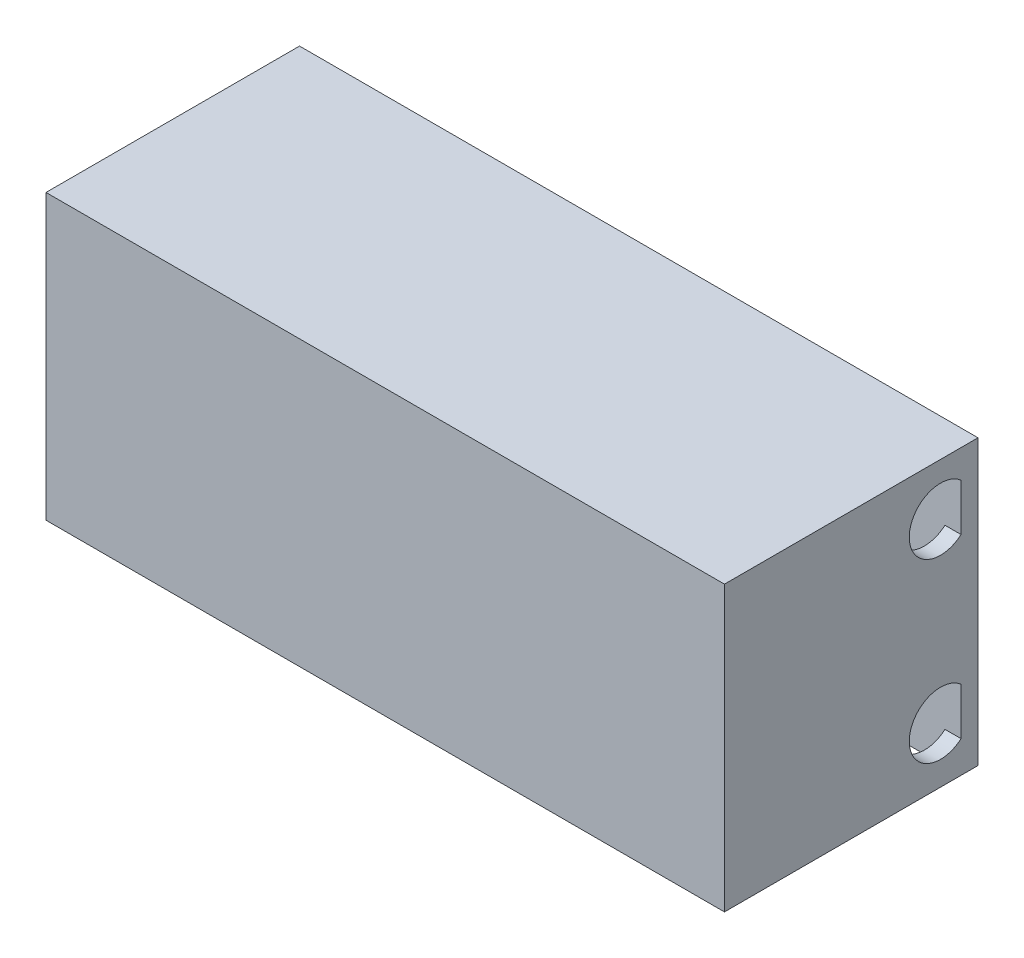
SolidWorks part; units mm, degrees
ref_plane "Front" through (0, 0, 0) normal (0, 0, 1) x (1, 0, 0)
ref_plane "Top" through (0, 0, 0) normal (0, 1, 0) x (1, 0, 0)
ref_plane "Right" through (0, 0, 0) normal (1, 0, 0) x (0, 0, -1)
sketch "Sketch1" plane through (0, 0, 0) normal (0, 1, 0) x (1, 0, 0)
  line L1 (0, 0) -> (-76, 0)
  line L2 (0, 0) -> (0, 28.4)
  line L3 (0, 28.4) -> (-76, 28.4)
  line L4 (-76, 0) -> (-76, 28.4)
  dimension "D1" = 28.4
  dimension "D2" = 76
extrude "Boss-Extrude1" add sketch "Sketch1" along normal blind 1.8
sketch "Sketch2" plane through (0, 0, 0) normal (0, -1, 0) x (-1, 0, 0)
  line L0 (0, 0) -> (0, 28.4) construction
  line L1 (76, 28.4) -> (0, 28.4)
  line L2 (76, 28.4) -> (76, 26.6)
  line L3 (76, 26.6) -> (0, 26.6)
  line L4 (0, 28.4) -> (0, 26.6)
  dimension "D1" = 1.8
extrude "Boss-Extrude2" add sketch "Sketch2" along normal blind 30
sketch "Sketch3" plane through (0, 0, 0) normal (0, -1, 0) x (-1, 0, 0)
  line L0 (0, 26.6) -> (76, 26.6) construction
  line L1 (76, 0) -> (74.2, 0)
  line L2 (76, 0) -> (76, 26.6)
  line L3 (76, 26.6) -> (74.2, 26.6)
  line L4 (74.2, 0) -> (74.2, 26.6)
  line L6 (0, 0) -> (1.8, 0)
  line L7 (0, 0) -> (0, 26.6)
  line L8 (0, 26.6) -> (1.8, 26.6)
  line L9 (1.8, 0) -> (1.8, 26.6)
  dimension "D1" = 1.8
  dimension "D2" = 1.8
extrude "Boss-Extrude3" add sketch "Sketch3" along normal blind 30
sketch "Sketch4" plane through (0, 0, 0) normal (0, -1, 0) x (-1, 0, 0)
  line L0 (1.8, 0) -> (1.8, 26.6) construction
  line L1 (1.8, 18.5) -> (74.2, 18.5)
  line L2 (1.8, 18.5) -> (1.8, 19.7)
  line L3 (1.8, 19.7) -> (74.2, 19.7)
  line L4 (74.2, 18.5) -> (74.2, 19.7)
  line L5 (74.2, 26.6) -> (74.2, 0) construction
  line L6 (1.8, 26.6) -> (74.2, 26.6) construction
  line L7 (1.8, 21.5) -> (74.2, 21.5)
  line L8 (1.8, 21.5) -> (1.8, 22.7)
  line L9 (1.8, 22.7) -> (74.2, 22.7)
  line L10 (74.2, 21.5) -> (74.2, 22.7)
  dimension "D1" = 1.2
  dimension "D2" = 1.2
  dimension "D3" = 1.8
  dimension "D4" = 3.9
extrude "Boss-Extrude4" add sketch "Sketch4" along normal blind 1
sketch "Sketch5" plane through (0, -1, 0) normal (0, -1, 0) x (-1, 0, 0)
  line L0 (74.2, 19.7) -> (1.8, 19.7) construction
  line L1 (1.8, 18.5) -> (6.8, 18.5)
  line L2 (1.8, 18.5) -> (1.8, 19.7)
  line L3 (1.8, 19.7) -> (6.8, 19.7)
  line L4 (6.8, 18.5) -> (6.8, 19.7)
  line L6 (74.2, 18.5) -> (69.2, 18.5)
  line L7 (74.2, 18.5) -> (74.2, 19.7)
  line L8 (74.2, 19.7) -> (69.2, 19.7)
  line L9 (69.2, 18.5) -> (69.2, 19.7)
  dimension "D1" = 5
  dimension "D2" = 5
extrude "Boss-Extrude5" add sketch "Sketch5" along normal blind 28
sketch "Sketch6" plane through (-74.2, 0, 0) normal (1, 0, 0) x (0, 0, -1)
  line L1 (21.5, -1) -> (24.3, -1)
  line L2 (21.5, -1) -> (21.5, -11)
  line L3 (21.5, -11) -> (24.3, -11)
  line L4 (24.3, -1) -> (24.3, -11)
  point P5 (0, 0)
  dimension "D1" = 2.8
  dimension "D2" = 10
extrude "Cut-Extrude1" cut sketch "Sketch6" against normal blind 2
sketch "Sketch7" plane through (0, 0, 0) normal (0, -1, 0) x (-1, 0, 0)
  line L0 (1.8, 21.5) -> (74.2, 21.5) construction
  line L1 (69.2, 24.3) -> (74.2, 24.3)
  line L2 (69.2, 24.3) -> (69.2, 25.5)
  line L3 (69.2, 25.5) -> (74.2, 25.5)
  line L4 (74.2, 24.3) -> (74.2, 25.5)
  line L5 (74.2, 26.6) -> (74.2, 22.7) construction
  dimension "D1" = 2.8
  dimension "D2" = 1.2
  dimension "D3" = 5
  dimension "D4" = 0
extrude "Boss-Extrude6" add sketch "Sketch7" along normal blind 10
sketch "Sketch8" plane through (0, -1, 0) normal (0, -1, 0) x (-1, 0, 0)
  line L0 (74.2, 22.7) -> (1.8, 22.7) construction
  line L1 (1.8, 21.5) -> (9.8, 21.5)
  line L2 (1.8, 21.5) -> (1.8, 22.7)
  line L3 (1.8, 22.7) -> (9.8, 22.7)
  line L4 (9.8, 21.5) -> (9.8, 22.7)
  dimension "D1" = 8
extrude "Cut-Extrude2" cut sketch "Sketch8" against normal blind 0.7
sketch "Sketch9" plane through (0, 0, 0) normal (0, -1, 0) x (-1, 0, 0)
  line L0 (1.8, 22.7) -> (1.8, 26.6) construction
  line L1 (11.8, 26.6) -> (1.8, 26.6)
  line L2 (11.8, 26.6) -> (11.8, 26.5)
  line L3 (11.8, 26.5) -> (1.8, 26.5)
  line L4 (1.8, 26.6) -> (1.8, 26.5)
  line L5 (74.2, 19.7) -> (1.8, 19.7) construction
  dimension "D1" = 0.1
  dimension "D2" = 6.8
  dimension "D3" = 10
extrude "Boss-Extrude7" add sketch "Sketch9" along normal blind 30
sketch "Sketch10" plane through (-1.8, 0, 0) normal (-1, 0, 0) x (0, 0, 1)
  line L0 (-19.7, -29) -> (-19.7, 0) construction
  line L1 (-22.7, 0) -> (-26.5, 0) construction
  line L2 (-26.5, -6.6382) -> (-26.5, -1.3618)
  line L3 (-26.5, -30) -> (-26.5, 0) construction
  line L4 (-26.5, -21.1618) -> (-26.5, -26.4382)
  line L6 (-26.5, -30) -> (-26.5, 0) construction
  arc A0 (-26.5, -6.6382) -> (-26.5, -1.3618) centre (-24.2, -4) ccw
  arc A1 (-26.5, -26.4382) -> (-26.5, -21.1618) centre (-24.2, -23.8) ccw
  dimension "D1" = 7
  dimension "D2" = 7
  dimension "D3" = 4.5
  dimension "D4" = 4.5
  dimension "D5" = 4
  dimension "D6" = 19.8
extrude "Cut-Extrude3" cut sketch "Sketch10" against normal blind 2
sketch "Sketch11" plane through (0, -1, 0) normal (0, -1, 0) x (-1, 0, 0)
  line L1 (6.8, 18.5) -> (69.2, 18.5)
  line L2 (6.8, 18.5) -> (6.8, 19.7)
  line L3 (6.8, 19.7) -> (69.2, 19.7)
  line L4 (69.2, 18.5) -> (69.2, 19.7)
extrude "Boss-Extrude8" add sketch "Sketch11" along normal blind 28
sketch "Sketch12" plane through (0, 0, 0) normal (0, -1, 0) x (1, 0, 0)
  line L0 (-1.8, 0) -> (-1.8, -18.5) construction
  line L1 (-1.8, -8.3) -> (-74.2, -8.3)
  line L2 (-1.8, -8.3) -> (-1.8, -7.1)
  line L3 (-1.8, -7.1) -> (-74.2, -7.1)
  line L4 (-74.2, -8.3) -> (-74.2, -7.1)
  line L5 (-74.2, -18.5) -> (-74.2, 0) construction
  line L6 (-1.8, -18.5) -> (-74.2, -18.5) construction
  dimension "D1" = 10.2
  dimension "D2" = 1.2
extrude "Boss-Extrude9" add sketch "Sketch12" along normal blind 29
sketch "Sketch13" plane through (0, 0, 0) normal (0, -1, 0) x (-1, 0, 0)
  line L0 (1.8, 0) -> (1.8, 7.1) construction
  line L1 (1.8, 5.1) -> (74.2, 5.1)
  line L2 (1.8, 5.1) -> (1.8, 3.9)
  line L3 (1.8, 3.9) -> (74.2, 3.9)
  line L4 (74.2, 5.1) -> (74.2, 3.9)
  line L5 (74.2, 7.1) -> (74.2, 0) construction
  line L6 (1.8, 7.1) -> (74.2, 7.1) construction
  dimension "D1" = 1.2
  dimension "D2" = 2
extrude "Boss-Extrude10" add sketch "Sketch13" along normal blind 1
sketch "Sketch14" plane through (0, -1, 0) normal (0, -1, 0) x (-1, 0, 0)
  line L0 (1.8, 3.9) -> (74.2, 3.9) construction
  line L1 (74.2, 5.1) -> (69.2, 5.1)
  line L2 (74.2, 5.1) -> (74.2, 3.9)
  line L3 (74.2, 3.9) -> (69.2, 3.9)
  line L4 (69.2, 5.1) -> (69.2, 3.9)
  line L6 (1.8, 5.1) -> (13.8, 5.1)
  line L7 (1.8, 5.1) -> (1.8, 3.9)
  line L8 (1.8, 3.9) -> (13.8, 3.9)
  line L9 (13.8, 5.1) -> (13.8, 3.9)
  dimension "D1" = 12
  dimension "D2" = 5
extrude "Boss-Extrude11" add sketch "Sketch14" along normal blind 5
sketch "Sketch15" plane through (0, 0, -7.1) normal (0, 0, 1) x (1, 0, 0)
  line L1 (-1.8, -29) -> (-7.8, -29)
  line L2 (-1.8, -29) -> (-1.8, -24)
  line L3 (-1.8, -24) -> (-7.8, -24)
  line L4 (-7.8, -29) -> (-7.8, -24)
  line L5 (-1.8, 0) -> (-7.8, 0)
  line L6 (-1.8, 0) -> (-1.8, -5)
  line L7 (-1.8, -5) -> (-7.8, -5)
  line L8 (-7.8, 0) -> (-7.8, -5)
  dimension "D1" = 6
  dimension "D2" = 6
  dimension "D3" = 5
  dimension "D4" = 5
extrude "Boss-Extrude12" add sketch "Sketch15" along normal blind 2
sketch "Sketch16" plane through (-74.2, 0, 0) normal (1, 0, 0) x (0, 0, -1)
  line L0 (3.9, 0) -> (0, 0) construction
  line L1 (4.1, -20) -> (6.5, -20)
  line L2 (4.1, -20) -> (4.1, -6.5)
  line L3 (4.1, -6.5) -> (6.5, -6.5)
  line L4 (6.5, -20) -> (6.5, -6.5)
  line L5 (7.1, -29) -> (7.1, 0) construction
  dimension "D1" = 13.5
  dimension "D2" = 2.4
  dimension "D3" = 6.5
  dimension "D4" = 0.6
extrude "Cut-Extrude4" cut sketch "Sketch16" against normal blind 2
sketch "Sketch17" plane through (0, 0, 0) normal (0, -1, 0) x (-1, 0, 0)
  line L0 (1.8, 0) -> (1.8, 3.9) construction
  line L1 (1.8, 1.8) -> (74.2, 1.8)
  line L2 (1.8, 1.8) -> (1.8, 0)
  line L3 (1.8, 0) -> (74.2, 0)
  line L4 (74.2, 1.8) -> (74.2, 0)
  line L5 (74.2, 3.9) -> (74.2, 0) construction
  line L6 (7.8, 7.1) -> (74.2, 7.1) construction
  dimension "D1" = 5.3
  dimension "D2" = 1.8
extrude "Boss-Extrude13" add sketch "Sketch17" along normal blind 30
fillet "Fillet1" radius 4 8 edges at (-38, 0, -8.3) (-38, 0, -18.5) (-1.8, -14.5, -18.5) (-1.8, -14.5, -8.3) (-74.2, -14.5, -8.3) (-74.2, -14.5, -18.5) (-74.2, -5, -25.5) (-71.7, 0, -25.5)
sketch "Sketch19" plane through (0, 0, 0) normal (0, -1, 0) x (-1, 0, 0)
  line L0 (1.8, 19.7) -> (1.8, 21.5) construction
  line L1 (1.8, 19.7) -> (4.1, 19.7)
  line L2 (1.8, 19.7) -> (1.8, 21.2)
  line L3 (1.8, 21.2) -> (4.1, 21.2)
  line L4 (4.1, 19.7) -> (4.1, 21.2)
  line L5 (74.2, 19.7) -> (1.8, 19.7) construction
  dimension "D1" = 2.3
  dimension "D2" = 1.5
extrude "Boss-Extrude14" add sketch "Sketch19" along normal blind 29
fillet "Fillet2" radius 4 1 edges at (-38, 0, -3.9)
fillet "Fillet3" radius 4 2 edges at (-74.2, -1.4706, -3.3351) (-74.2, -4.76, -3.9)
fillet "Fillet4" radius 4 2 edges at (-1.8, -1.4706, -3.3351) (-1.8, -4.76, -3.9)
sketch "Sketch18" plane through (-74.2, 0, 0) normal (1, 0, 0) x (0, 0, -1)
  line L1 (21.5, -11) -> (20.5, -11)
  line L2 (21.5, -11) -> (21.5, -1)
  line L3 (21.5, -1) -> (20.5, -1)
  line L4 (20.5, -11) -> (20.5, -1)
  dimension "D1" = 10
  dimension "D2" = 1
extrude "Cut-Extrude5" cut sketch "Sketch18" against normal blind 2
